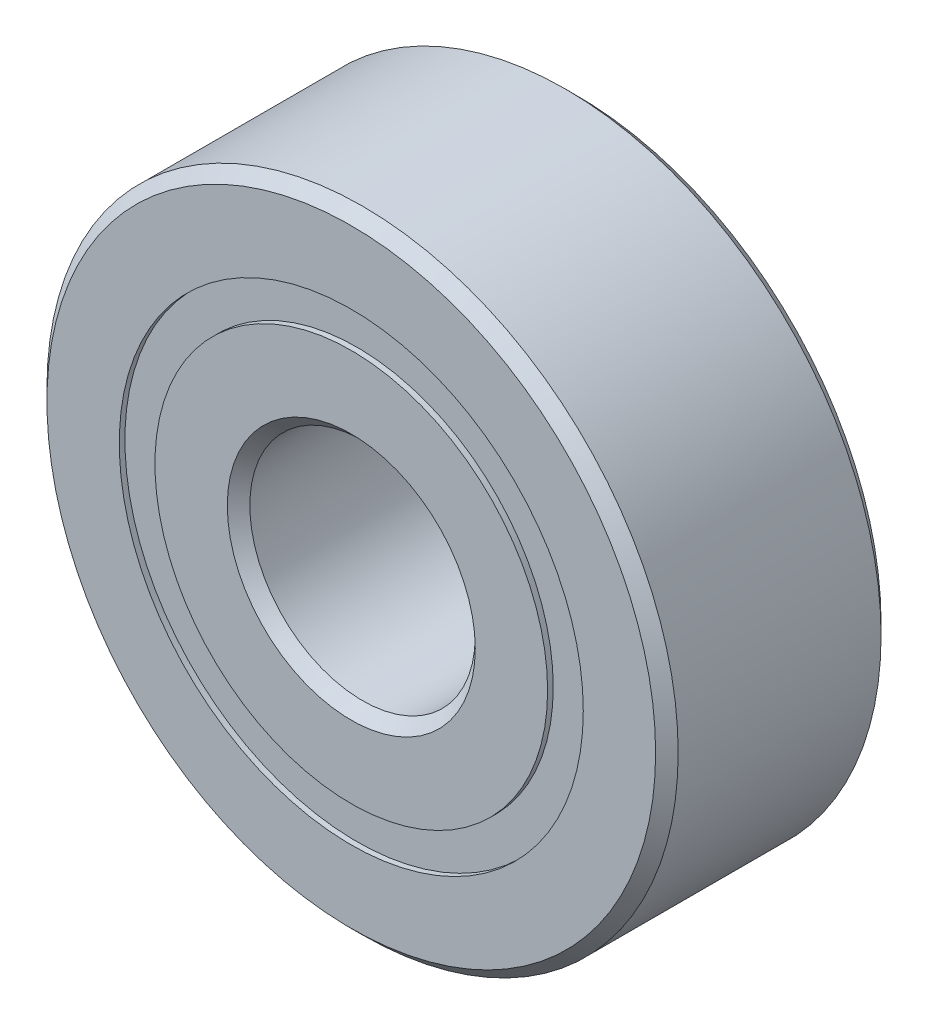
SolidWorks part; units mm, degrees
ref_plane "Front Plane" through (0, 0, 0) normal (0, 0, 1) x (1, 0, 0)
ref_plane "Top Plane" through (0, 0, 0) normal (0, 1, 0) x (1, 0, 0)
ref_plane "Right Plane" through (0, 0, 0) normal (1, 0, 0) x (0, 0, -1)
sketch "Sketch1" plane through (0, 0, 0) normal (1, 0, 0) x (0, 0, -1)
  line L0 (-2.5, 0) -> (2.5, 0) construction
  line L1 (0, 7) -> (0, -7) construction
  line L2 (2.25, 7) -> (-2.25, 7)
  line L3 (-2.25, 7) -> (-2.5, 6.75)
  line L4 (-2.5, 6.75) -> (-2.5, 5.1456)
  line L5 (-2.5, 5.1456) -> (-1.1111, 5.1456)
  line L6 (2.5, 5.1456) -> (1.1111, 5.1456)
  line L7 (2.5, 6.75) -> (2.5, 5.1456)
  line L8 (2.25, 7) -> (2.5, 6.75)
  line L9 (0, 7) -> (0, 4.75) construction
  line L10 (0, 4.75) -> (0, 2.5) construction
  arc A0 (-1.1111, 5.1456) -> (1.1111, 5.1456) centre (0, 4.75) cw
  point P14 (0, 2.5)
  dimension "Width" = 5
  dimension "OD" = 14
  dimension "D1" = 45
  dimension "D2" = 0.25
  dimension "Shaft Dia" = 5
  dimension "D3" = 2.2222
  dimension "D4" = 0.3956
revolve "Revolve1" add sketch "Sketch1" angle 360 about L0
sketch "Sketch3" plane through (0, 0, 0) normal (1, 0, 0) x (0, 0, -1)
  line L0 (-2.5, 4.3544) -> (-1.1111, 4.3544)
  line L1 (0, 7) -> (0, -7) construction
  line L2 (-2.5, 6.75) -> (-2.5, 5.1456) construction
  line L3 (-2.5, 4.3544) -> (-2.5, 2.75)
  line L4 (-2.25, 7) -> (-2.5, 6.75) construction
  line L5 (-2.5, 2.75) -> (-2.25, 2.5)
  line L6 (-2.25, 2.5) -> (2.25, 2.5)
  line L7 (2.25, 7) -> (2.25, -7) construction
  line L8 (2.25, 2.5) -> (2.5, 2.75)
  line L9 (2.5, -6.75) -> (2.5, 6.75) construction
  line L10 (2.5, 2.75) -> (2.5, 4.3544)
  line L11 (2.5, 4.3544) -> (1.1111, 4.3544)
  line L13 (2.25, 7) -> (2.5, 6.75) construction
  arc A0 (1.1111, 5.1456) -> (-1.1111, 5.1456) centre (0, 4.75) ccw construction
  arc A1 (1.1111, 4.3544) -> (-1.1111, 4.3544) centre (0, 4.75) cw
revolve "Revolve3" add sketch "Sketch3" angle 360 about L0
sketch "Sketch4" plane through (0, 0, 0) normal (1, 0, 0) x (0, 0, -1)
  line L0 (-1.1794, 4.75) -> (1.1794, 4.75)
  arc A2 (-1.1794, 4.75) -> (1.1794, 4.75) centre (0, 4.75) cw
  arc A3 (1.1111, 5.1456) -> (-1.1111, 5.1456) centre (0, 4.75) ccw construction
revolve "Revolve4" add sketch "Sketch4" angle 360 about L0
ref_axis "Axis1" through (0, 0, -2.5) along (0, 0, 1)
pattern_circular "CirPattern1" count 12 every 30 about axis through (0, 0, -2.5) along (0, 0, 1) of bodies 104
sketch "Sketch5" plane through (0, 0, 0) normal (1, 0, 0) x (0, 0, -1)
  line L0 (-2.5, 5.1456) -> (-1.1111, 5.1456) construction
  line L1 (-2.375, 5.1456) -> (-1.1794, 5.1456)
  line L2 (-2.375, 5.1456) -> (-2.375, 4.3544)
  line L3 (-2.375, 4.3544) -> (-1.1794, 4.3544)
  line L4 (-1.1794, 5.1456) -> (-1.1794, 4.3544)
  line L5 (-2.5, 4.3544) -> (-1.1111, 4.3544) construction
  line L6 (2.5, 5.1456) -> (1.1111, 5.1456) construction
  line L7 (2.375, 5.1456) -> (1.1794, 5.1456)
  line L8 (2.375, 5.1456) -> (2.375, 4.3544)
  line L9 (2.375, 4.3544) -> (1.1794, 4.3544)
  line L10 (1.1794, 5.1456) -> (1.1794, 4.3544)
  line L11 (2.5, 4.3544) -> (1.1111, 4.3544) construction
  line L12 (-2.25, 7) -> (-2.5, 6.75) construction
  point P18 (-2.375, 6.875)
revolve "Revolve5" add sketch "Sketch5" angle 360 about L0
sketch "Sketch6" plane through (0, 0, 0) normal (1, 0, 0) x (0, 0, -1)
  line L0 (2.5, 0) -> (-2.5, 0) construction
  line L1 (2.5, 5.1456) -> (1.4, 5.1456)
  line L2 (2.5, 5.1456) -> (2.5, 9.5)
  line L3 (2.5, 9.5) -> (1.4, 9.5)
  line L4 (1.4, 5.1456) -> (1.4, 9.5)
  dimension "Th" = 1.1
  dimension "Flange OD" = 19
revolve "Revolve6" [suppressed] add sketch "Sketch6" angle 360 about L0
equation "\"D2@Sketch1\" = \"Width@Sketch1\"*.05"
equation "\"D3@Sketch1\" = \"Width@Sketch1\"/2.25"
equation "\"D4@Sketch1\" = (((\"OD@Sketch1\"-\"Width@Sketch1\")/2)/3.25)/3.5"
equation "\"D2@CirPattern1\" = 360/\"Balls@CirPattern1\""
